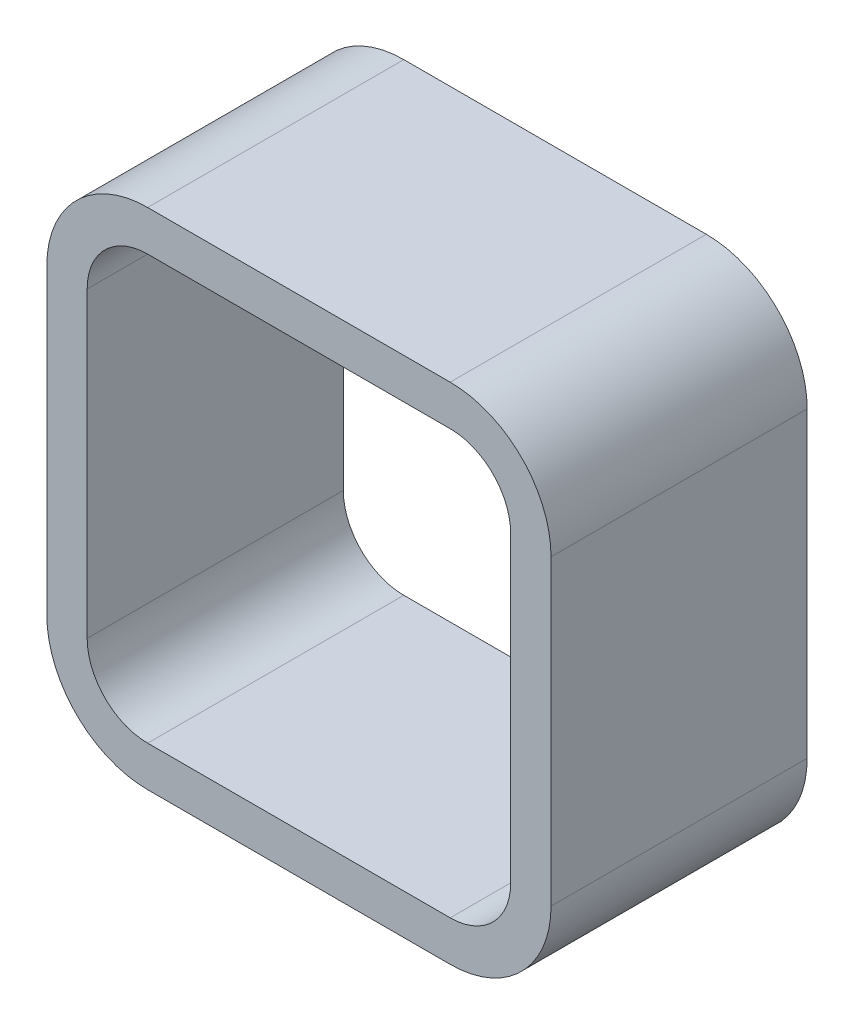
SolidWorks part; units mm, degrees
ref_plane "Front Plane" through (0, 0, 0) normal (0, 0, 1) x (1, 0, 0)
ref_plane "Top Plane" through (0, 0, 0) normal (0, 1, 0) x (1, 0, 0)
ref_plane "Right Plane" through (0, 0, 0) normal (1, 0, 0) x (0, 0, -1)
sketch "Sketch1" plane through (0, 0, 0) normal (0, 0, 1) x (1, 0, 0)
  line L0 (-15, 21) -> (15, 21)
  line L1 (-15, -25) -> (15, -25)
  line L2 (-25, -15) -> (-25, 15)
  line L3 (-15, 25) -> (15, 25)
  line L4 (25, -15) -> (25, 15)
  line L5 (-25, -25) -> (25, 25) construction
  line L6 (-25, 25) -> (25, -25) construction
  line L7 (21, -15) -> (21, 15)
  line L8 (-15, -21) -> (15, -21)
  line L9 (-21, -15) -> (-21, 15)
  arc A0 (-25, 15) -> (-15, 25) centre (-15, 15) cw
  arc A1 (15, 25) -> (25, 15) centre (15, 15) cw
  arc A2 (-15, -25) -> (-25, -15) centre (-15, -15) cw
  arc A3 (15, -25) -> (25, -15) centre (15, -15) ccw
  arc A4 (-21, 15) -> (-15, 21) centre (-15, 15) cw
  arc A5 (15, 21) -> (21, 15) centre (15, 15) cw
  arc A6 (15, -21) -> (21, -15) centre (15, -15) ccw
  arc A7 (-15, -21) -> (-21, -15) centre (-15, -15) cw
  point P0 (0, 0)
  dimension "D2" = 10
  dimension "Thickness" = 4
extrude "BaseSection" add sketch "Sketch1" along normal mid plane 25.4
equation "\"D2@Sketch1\" = \"Thickness@Sketch1\" * (  (IIf(\"Thickness@Sketch1\">3, 1.5, 1))  + 1 ) "
